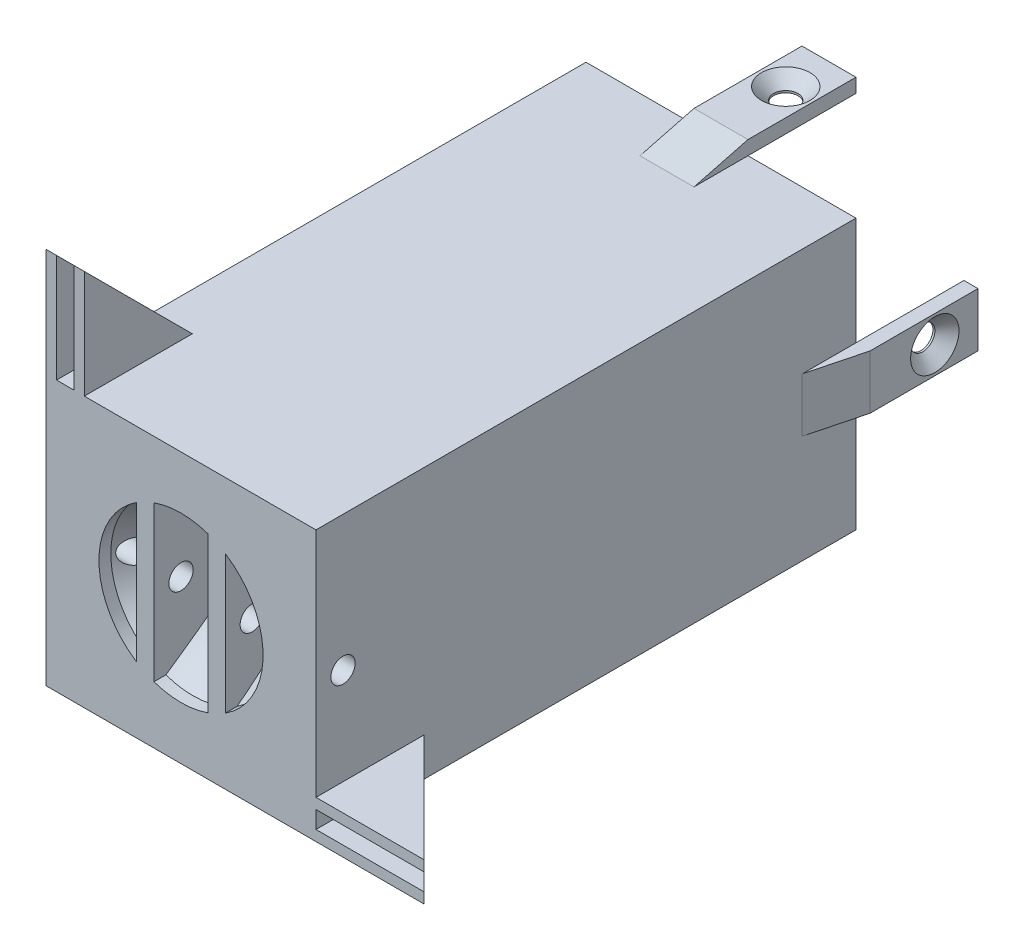
SolidWorks part; units mm, degrees
ref_plane "Alzado" through (0, 0, 0) normal (0, 0, 1) x (1, 0, 0)
ref_plane "Planta" through (0, 0, 0) normal (0, 1, 0) x (1, 0, 0)
ref_plane "Vista lateral" through (0, 0, 0) normal (1, 0, 0) x (0, 0, -1)
sketch "Croquis1" plane through (0, 0, 0) normal (0, 0, 1) x (1, 0, 0)
  line L1 (25, -25) -> (-25, -25)
  line L2 (25, -25) -> (25, 25)
  line L3 (25, 25) -> (-25, 25)
  line L4 (-25, -25) -> (-25, 25)
  line L5 (25, -25) -> (-25, 25) construction
  line L6 (25, 25) -> (-25, -25) construction
  circle A0 centre (0, 0) radius 2
  point P0 (0, 0)
  dimension "D3" = 4
  dimension "D1" = 50
  dimension "D2" = 50
extrude "Saliente-Extruir2" add sketch "Croquis1" along normal blind 100
ref_plane "Plano1" through (0, 0, 0) normal (1, 0, 0) x (0, 0, -1)
sketch "Croquis2" plane through (0, 0, 0) normal (1, 0, 0) x (0, 0, -1)
  line L1 (-100, 25) -> (-100, -25) construction
  line L4 (-100, 15.2) -> (-100, 0)
  line L6 (-97.8, 15.2) -> (-89.8, 10)
  line L7 (-100, 15.2) -> (-97.8, 15.2)
  line L8 (-89.8, 0) -> (-89.8, 10)
  line L9 (-100, 0) -> (-89.8, 0)
  dimension "D1" = 2.2
  dimension "D2" = 10.2
  dimension "D3" = 10
  dimension "D4" = 15.2
revolve "Cortar-Revolución1" cut sketch "Croquis2" angle 360 about L9
sketch "Croquis4" plane through (0, 0, 100) normal (0, 0, 1) x (1, 0, 0)
  line L0 (0, -0.44) -> (0, 0.44) construction
  line L1 (-8.2, 20) -> (-5, 20)
  line L2 (-8.2, 20) -> (-8.2, -20)
  line L3 (-8.2, -20) -> (-5, -20)
  line L4 (-5, 20) -> (-5, -20)
  line L5 (8.2, -20) -> (5, -20)
  line L6 (5, 20) -> (5, -20)
  line L7 (8.2, 20) -> (5, 20)
  line L8 (8.2, 20) -> (8.2, -20)
  point P6 (-5, 0)
  dimension "D1" = 3.2
  dimension "D2" = 5
  dimension "D3" = 40
extrude "Saliente-Extruir5" add sketch "Croquis4" along direction (0, 0, 1) on the side against the normal up to surface (10.2 mm away) up to face at (0, -2, 89.8)
sketch "Croquis8" plane through (0, 0, 89.8) normal (0, 0, 1) x (1, 0, 0)
  circle A0 centre (0, 0) radius 4
  dimension "D1" = 8
extrude "Cortar-Extruir3" cut sketch "Croquis8" against normal offset from surface (87.4 mm away) 2.4 up to face at (0, 0, 0)
sketch "Croquis7" plane through (-25, 0, 0) normal (-1, 0, 0) x (0, 0, 1)
  line L1 (100, 25) -> (100, -25) construction
  circle A0 centre (95, 0) radius 2
  dimension "D1" = 4
  dimension "D2" = 5
extrude "Cortar-Extruir2" cut sketch "Croquis7" against normal up to vertex (50 mm away) up to point (25, -25, 100)
hole_wizard "Refrentado para tornillo tapón con cabeza plana de clavija de M41" positions "Croquis10" profile "Croquis11" countersink size "M4" standard "Ansi Metric" end condition through all
sketch "Croquis10" plane through (-25, 0, 0) normal (-1, 0, 0) x (0, 0, 1)
  point P0 (95, 0)
sketch "Croquis11" plane through (-25, 0, 95) normal (0, 1, 0) x (0, 0, 1)
  line L0 (0, 0) -> (0, 50)
  line L1 (0, 50) -> (2.25, 50)
  line L2 (2.25, 50) -> (2.25, 2.23)
  line L3 (2.25, 2.23) -> (4.48, 0)
  line L5 (4.48, 0) -> (0, 0)
  line L6 (-2.25, 2.23) -> (-4.48, 0) construction
  line L11 (0, -6.35) -> (0, 107.95) construction
  dimension "Diámetro de taladro hasta el siguiente" = 4.5
  dimension "Profundidad de taladro hasta el siguiente" = 50
  dimension "Diámetro de avellanado cercano" = 8.96
  dimension "Ángulo de avellanado cercano" = 90
sketch "Croquis12" plane through (-25, 0, 0) normal (-1, 0, 0) x (0, 0, 1)
  line L2 (100, 0) -> (0, 0) construction
  line L5 (100, 25) -> (100, -25) construction
  line L6 (0, 25) -> (0, -25) construction
  line L7 (100, 45) -> (80, 25)
  line L8 (100, 25) -> (100, 45)
  line L9 (100, 25) -> (80, 25)
extrude "Saliente-Extruir6" add sketch "Croquis12" against normal blind 1.95
extrude "Saliente-Extruir7" add sketch "Croquis12<2>" against normal blind 1.95 from offset 5.15 offset against normal yes
sketch "Croquis12<2>" plane through (-25, 0, 0) normal (-1, 0, 0) x (0, 0, 1) same geometry as "Croquis12"
sketch "Croquis15" plane through (0, -25, 0) normal (0, -1, 0) x (1, 0, 0)
  line L0 (25, 100) -> (25, 80)
  line L1 (25, 100) -> (25, 0) construction
  line L2 (25, 80) -> (45, 100)
  line L3 (45, 100) -> (25, 100)
  dimension "D1" = 20
  dimension "D2" = 20
extrude "Saliente-Extruir9" add sketch "Croquis15" against normal blind 1.95
extrude "Saliente-Extruir10" add sketch "Croquis15<2>" against normal blind 1.95 from offset 5.15 offset against normal yes
sketch "Croquis15<2>" plane through (0, -25, 0) normal (0, -1, 0) x (1, 0, 0) same geometry as "Croquis15"
sketch "Croquis16" plane through (25, 0, 0) normal (1, 0, 0) x (0, 0, -1)
  line L0 (0, 25) -> (-10, 25)
  line L1 (-100, 25) -> (0, 25) construction
  line L2 (-10, 25) -> (0, 27.6)
  line L3 (0, 27.6) -> (20, 27.6)
  line L4 (20, 27.6) -> (20, 25)
  line L5 (20, 25) -> (0, 25)
  dimension "D1" = 20
  dimension "D2" = 2.6
  dimension "D3" = 10
extrude "Saliente-Extruir11" add sketch "Croquis16" against normal blind 5 and the other way blind 5 from offset 25 offset against normal yes
sketch "Croquis17" plane through (0, 27.6, 0) normal (0, 1, 0) x (1, 0, 0)
  line L0 (5, 20) -> (-5, 20) construction
  circle A0 centre (0, 12) radius 2.25
  dimension "D1" = 4.5
  dimension "D2" = 8
extrude "Cortar-Extruir4" cut sketch "Croquis17" against normal up to vertex (2.6 mm away) up to point (-5, 25, -20)
hole_wizard "Refrentado para tornillo tapón con cabeza plana de clavija de M42" positions "Croquis18" profile "Croquis19" countersink size "M4" standard "Ansi Metric" end condition through all
sketch "Croquis18" plane through (0, 27.6, 0) normal (0, 1, 0) x (1, 0, 0)
  point P0 (0, 12)
sketch "Croquis19" plane through (0, 27.6, -12) normal (1, 0, 0) x (0, 0, 1)
  line L0 (0, 0) -> (0, 52.6)
  line L1 (0, 52.6) -> (2.25, 52.6)
  line L2 (2.25, 52.6) -> (2.25, 2.23)
  line L3 (2.25, 2.23) -> (4.48, 0)
  line L5 (4.48, 0) -> (0, 0)
  line L6 (-2.25, 2.23) -> (-4.48, 0) construction
  line L11 (0, -6.35) -> (0, 107.95) construction
  dimension "Diámetro de taladro hasta el siguiente" = 4.5
  dimension "Profundidad de taladro hasta el siguiente" = 52.6
  dimension "Diámetro de avellanado cercano" = 8.96
  dimension "Ángulo de avellanado cercano" = 90
ref_axis "Eje1" through (25, 25, 0) along (-0.7071, -0.7071, 0)
ref_plane "Plano2" through (0, 0, 0) normal (0.7071, -0.7071, 0) x (-0.7071, -0.7071, 0)
mirror "Simetría1" about plane through (0, 0, 0) normal (0.7071, -0.7071, 0) of "Refrentado para tornillo tapón con cabeza plana de clavija de M42", "Cortar-Extruir4", "Saliente-Extruir11"
